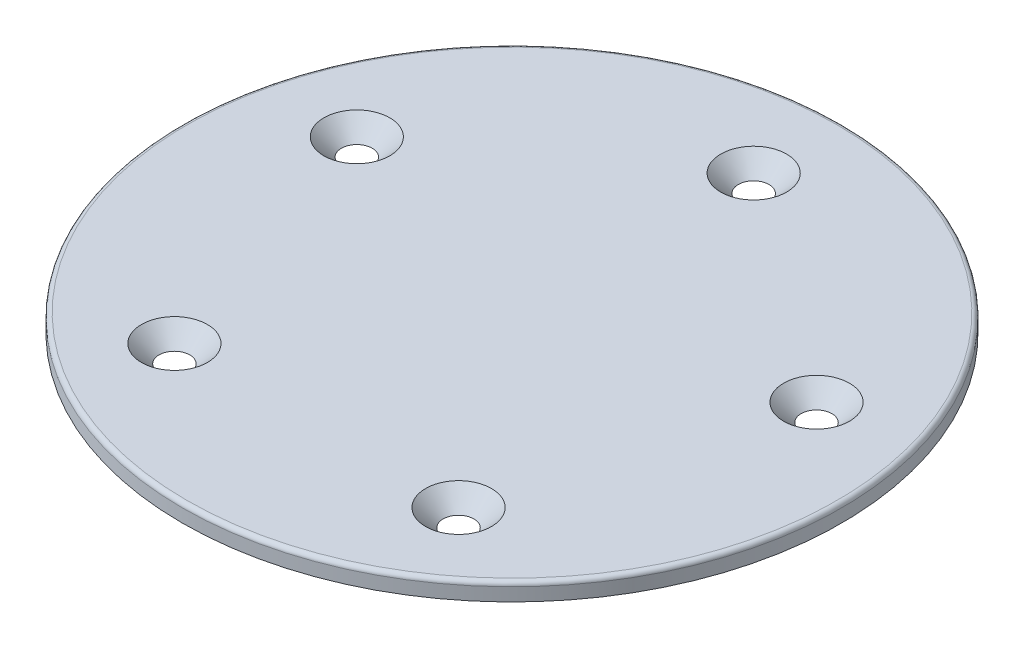
SolidWorks part; units mm, degrees
ref_plane "Front Plane" through (0, 0, 0) normal (0, 0, 1) x (1, 0, 0)
ref_plane "Top Plane" through (0, 0, 0) normal (0, 1, 0) x (1, 0, 0)
ref_plane "Right Plane" through (0, 0, 0) normal (1, 0, 0) x (0, 0, -1)
sketch "Sketch2" plane through (0, 0, 0) normal (0, 1, 0) x (1, 0, 0)
  circle A0 centre (0, 0) radius 37.5
  circle A1 centre (0, 0) radius 27.5
  circle A2 centre (0, 27.5) radius 1.75
  circle A3 centre (26.1541, 8.498) radius 1.75
  circle A4 centre (16.1641, -22.248) radius 1.75
  circle A5 centre (-16.1641, -22.248) radius 1.75
  circle A6 centre (-26.1541, 8.498) radius 1.75
  point P16 (0, 0)
  dimension "D1" = 75
  dimension "D2" = 55
  dimension "D4" = 3.5
  dimension "D3" = 5
extrude "Boss-Extrude1" add sketch "Sketch2" along normal blind 2 contours A0 A6 A1 A2 A3 A4 A5 | A6 A1 A5 A4 A3 A2 region at (-36.4393, 0, 0) region at (0, 0, 0)
chamfer "Chamfer1" distance 2 5 edges at (-16.1641, 2, 23.998) (16.1641, 2, 23.998) (26.1541, 2, -6.748) (0, 2, -25.75) (-26.1541, 2, -6.748)
fillet "Fillet1" radius 0.5 1 edges at (0, 2, 37.5)
